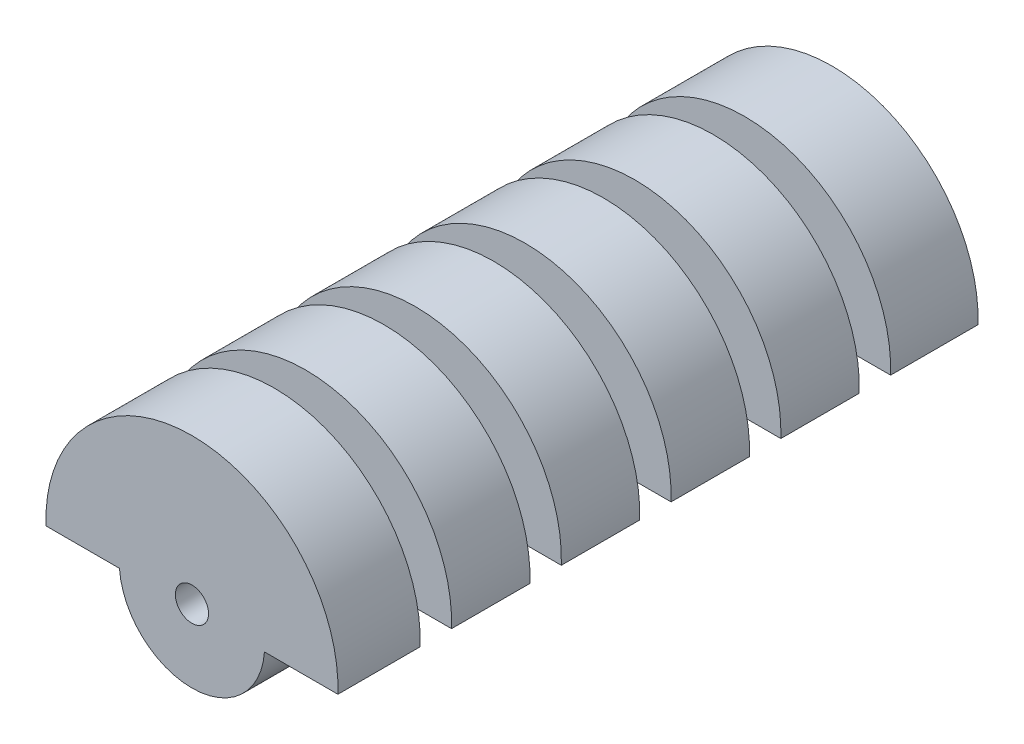
SolidWorks part; units mm, degrees
material "RUBBER 65A Test Modulus"
ref_plane "Front Plane" through (0, 0, 0) normal (0, 0, 1) x (1, 0, 0)
ref_plane "Top Plane" through (0, 0, 0) normal (0, 1, 0) x (1, 0, 0)
ref_plane "Right Plane" through (0, 0, 0) normal (1, 0, 0) x (0, 0, -1)
sketch "Sketch3" plane through (0, 0, 0) normal (0, 0, 1) x (1, 0, 0)
  circle A0 centre (0, 0) radius 27.94
  dimension "D1" = 55.88
extrude "Boss-Extrude2" add sketch "Sketch3" along normal blind 122.46
ref_axis "Axis2" through (0, 0, 121.5887) along (0, 0, -1)
sketch "Sketch5" plane through (0, 0, 122.46) normal (0, 0, 1) x (1, 0, 0)
  circle A0 centre (0, 0) radius 3.175
  dimension "D1" = 6.35
extrude "Cut-Extrude1" cut sketch "Sketch5" against normal through all contours A0
sketch "Sketch4" plane through (0, 0, 0) normal (0, 1, 0) x (1, 0, 0)
  line L0 (0, -122.46) -> (0, 0) construction
  line L1 (-27.94, -122.46) -> (27.94, -122.46) construction
  line L3 (-27.94, -106.72) -> (-13.94, -106.72)
  line L4 (-27.94, -106.72) -> (-27.94, -100.72)
  line L5 (-27.94, -100.72) -> (-13.94, -100.72)
  line L6 (-13.94, -106.72) -> (-13.94, -100.72)
  line L63 (-27.94, -85.72) -> (-27.94, -79.72)
  line L64 (-27.94, -85.72) -> (-13.94, -85.72)
  line L65 (-13.94, -85.72) -> (-13.94, -79.72)
  line L66 (-27.94, -79.72) -> (-13.94, -79.72)
  line L67 (-27.94, -64.72) -> (-27.94, -58.72)
  line L68 (-27.94, -64.72) -> (-13.94, -64.72)
  line L69 (-13.94, -64.72) -> (-13.94, -58.72)
  line L70 (-27.94, -58.72) -> (-13.94, -58.72)
  line L71 (-27.94, -43.72) -> (-27.94, -37.72)
  line L72 (-27.94, -43.72) -> (-13.94, -43.72)
  line L73 (-13.94, -43.72) -> (-13.94, -37.72)
  line L74 (-27.94, -37.72) -> (-13.94, -37.72)
  line L75 (-27.94, -22.72) -> (-27.94, -16.72)
  line L76 (-27.94, -22.72) -> (-13.94, -22.72)
  line L77 (-13.94, -22.72) -> (-13.94, -16.72)
  line L78 (-27.94, -16.72) -> (-13.94, -16.72)
  line L91 (-27.94, -106.72) -> (-27.94, -85.72) construction
  line L92 (-27.94, -1.72) -> (-27.94, 4.28) [skipped]
  line L93 (-27.94, -1.72) -> (-13.94, -1.72) [skipped]
  line L94 (-13.94, -1.72) -> (-13.94, 4.28) [skipped]
  line L95 (-27.94, 4.28) -> (-13.94, 4.28) [skipped]
  line L96 (-27.94, 19.28) -> (-27.94, 25.28) [skipped]
  line L97 (-27.94, 19.28) -> (-13.94, 19.28) [skipped]
  line L98 (-13.94, 19.28) -> (-13.94, 25.28) [skipped]
  line L99 (-27.94, 25.28) -> (-13.94, 25.28) [skipped]
  line L100 (-27.94, 40.28) -> (-27.94, 46.28) [skipped]
  line L101 (-27.94, 40.28) -> (-13.94, 40.28) [skipped]
  line L102 (-13.94, 40.28) -> (-13.94, 46.28) [skipped]
  line L103 (-27.94, 46.28) -> (-13.94, 46.28) [skipped]
  dimension "D1" = 15.74
  dimension "D2" = 6
  dimension "D3" = 27.94
  dimension "D4" = 14
  dimension "D6" = 21
  dimension "D5" = 8
revolve "Cut-Revolve1" cut sketch "Sketch4" angle 360 about L0
shell "Shell1" thickness 3
sketch "Sketch10" plane through (0, 0, 0) normal (0, 0, -1) x (-1, 0, 0)
  line L0 (0, 27.94) -> (0, -27.94) construction
  line L1 (-27.94, 0) -> (27.94, 0) construction
  line L2 (-1, 27.9221) -> (-1, 3.0134)
  line L3 (1, 3.0134) -> (1, 27.9221)
  line L4 (3.0134, 1) -> (27.9221, 1)
  line L5 (3.0134, -1) -> (27.9221, -1)
  line L6 (-1, -3.0134) -> (-1, -27.9221)
  line L7 (1, -3.0134) -> (1, -27.9221)
  line L8 (-27.9221, -1) -> (-3.0134, -1)
  line L9 (-27.9221, 1) -> (-3.0134, 1)
  circle A0 centre (0, 0) radius 27.94 construction
  circle A1 centre (0, 0) radius 3.175 construction
  arc A2 (-1, -27.9221) -> (1, -27.9221) centre (0, 0) ccw
  arc A3 (27.9221, -1) -> (27.9221, 1) centre (0, 0) ccw
  arc A4 (1, 27.9221) -> (-1, 27.9221) centre (0, 0) ccw
  arc A5 (-27.9221, 1) -> (-27.9221, -1) centre (0, 0) ccw
  arc A6 (-1, -3.0134) -> (1, -3.0134) centre (0, 0) ccw
  arc A7 (-3.0134, 1) -> (-3.0134, -1) centre (0, 0) ccw
  arc A8 (1, 3.0134) -> (-1, 3.0134) centre (0, 0) ccw
  arc A9 (3.0134, -1) -> (3.0134, 1) centre (0, 0) ccw
  dimension "D1" = 1
  dimension "D2" = 1
  dimension "D3" = 1
  dimension "D4" = 1
  dimension "D5" = 1
extrude "Boss-Extrude3" add sketch "Sketch10" against normal up to surface (122.46 mm away) up to face at (3.175, 0, 122.46)
ref_plane "Plane1" through (0, 0, 0) normal (-0.7071, -0.7071, 0) x (0, 0, -1)
ref_plane "Plane2" through (0, 0, 0) normal (-0.7071, 0.7071, 0) x (0, 0, -1)
ref_plane "Plane3" through (0, 0, 0) normal (0, 1, 0) x (1, 0, 0)
sketch "Sketch13" plane through (0, 0, 0) normal (0, 1, 0) x (1, 0, 0)
  line L0 (-30.3872, -37.72) -> (-13.9041, -37.72)
  line L1 (-30.3872, -16.72) -> (-13.9041, -16.72)
  line L2 (-30.3872, -16.72) -> (-30.3872, -22.72)
  line L3 (-30.3872, -22.72) -> (-13.9041, -22.72)
  line L4 (-13.9041, -16.72) -> (-13.9041, -22.72)
  line L5 (-30.3872, -37.72) -> (-30.3872, -43.72)
  line L6 (-30.3872, -43.72) -> (-13.9041, -43.72)
  line L7 (-13.9041, -37.72) -> (-13.9041, -43.72)
  line L8 (-30.3872, -58.72) -> (-13.9041, -58.72)
  line L9 (-30.3872, -58.72) -> (-30.3872, -64.72)
  line L10 (-30.3872, -64.72) -> (-13.9041, -64.72)
  line L11 (-13.9041, -58.72) -> (-13.9041, -64.72)
  line L12 (-30.3872, -79.72) -> (-13.9041, -79.72)
  line L13 (-30.3872, -79.72) -> (-30.3872, -85.72)
  line L14 (-30.3872, -85.72) -> (-13.9041, -85.72)
  line L15 (-13.9041, -79.72) -> (-13.9041, -85.72)
  line L16 (-30.3872, -100.72) -> (-13.9041, -100.72)
  line L17 (-30.3872, -100.72) -> (-30.3872, -106.72)
  line L18 (-30.3872, -106.72) -> (-13.9041, -106.72)
  line L19 (-13.9041, -100.72) -> (-13.9041, -106.72)
  dimension "D2" = 6
  dimension "D1" = 5
revolve "Cut-Revolve2" cut sketch "Sketch13" angle 360 about axis through (0, 0, 121.5887) along (0, 0, -1) other way angle 360
sketch "Sketch15" plane through (0, 0, 0) normal (0, 0, -1) x (-1, 0, 0)
  line L0 (0, 0) -> (0, 28.5004) construction
  line L1 (0, 0) -> (-22.0052, 22.0052) construction
sketch "Sketch16" plane through (0, 0, 0) normal (0, 0, -1) x (-1, 0, 0)
  line L0 (-3.175, 0) -> (-6.9755, 0) construction
  line L1 (-27.94, 0) -> (27.94, 0) construction
  line L2 (3.175, 0) -> (7.175, 0) construction
  line L3 (-6.9755, 0) -> (-6.9755, -0.971) construction
  line L4 (-6.9755, -0.971) -> (-6.6911, -0.971) construction
  line L5 (7.175, 0) -> (7.175, -1) construction
  line L8 (-3.175, 0) -> (-6.175, 0) construction
  line L9 (3.175, 0) -> (6.175, 0) construction
  line L10 (-27.9231, -0.971) -> (-6.0982, -0.971)
  line L11 (27.9221, -1) -> (6.0935, -1)
  arc A0 (-27.9231, -0.971) -> (27.9221, -1) centre (0, 0) ccw
  circle A1 centre (0, 0) radius 27.94 construction
  circle A2 centre (0, 0) radius 3.175 construction
  arc A5 (-6.0982, -0.971) -> (6.0935, -1) centre (0, 0) ccw
extrude "Cut-Extrude3" cut sketch "Sketch16" against normal blind 123
sketch "Sketch18" plane through (0, 0, 0) normal (0, 0, -1) x (-1, 0, 0)
  line L0 (-3.175, 0) -> (-13.9041, 0)
  line L1 (3.175, 0) -> (13.9041, 0)
  line L2 (-6.0982, -0.971) -> (-27.9231, -0.971) construction
  circle A0 centre (0, 0) radius 3.175 construction
  arc A1 (-3.175, 0) -> (3.175, 0) centre (0, 0) ccw
  arc A2 (-13.9041, 0) -> (13.9041, 0) centre (0, 0) ccw
extrude "Boss-Extrude5" add sketch "Sketch18" against normal blind 122.46
equation "\"inwall\"= .75"
equation "\"outwall\"=2"
